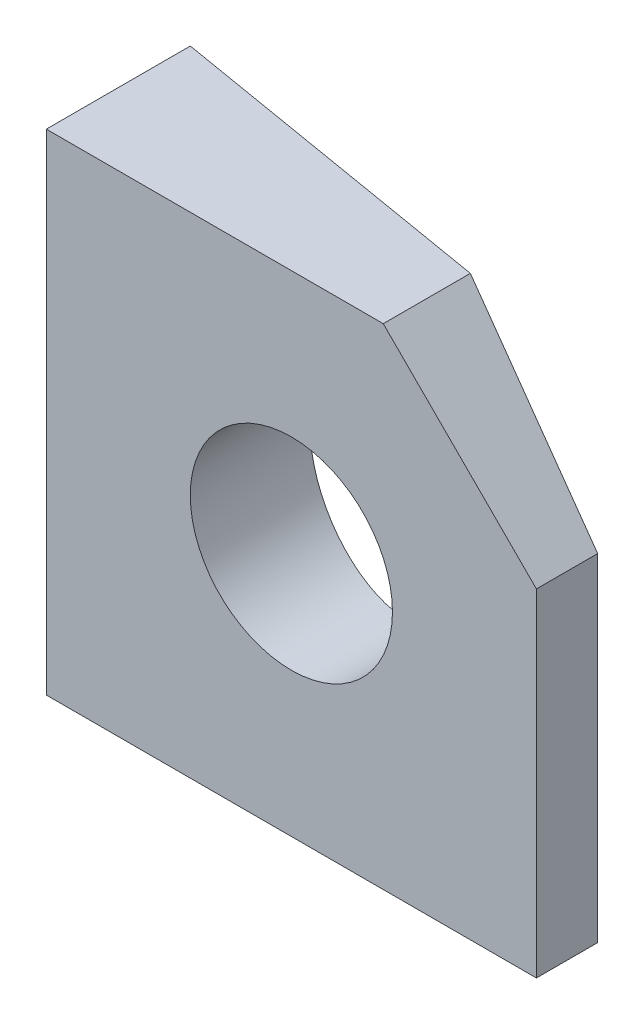
SolidWorks part; units mm, degrees
ref_plane "Front" through (0, 0, 0) normal (0, 0, 1) x (1, 0, 0)
ref_plane "Top" through (0, 0, 0) normal (0, 1, 0) x (1, 0, 0)
ref_plane "Right" through (0, 0, 0) normal (1, 0, 0) x (0, 0, -1)
sketch "Sketch1" plane through (0, 0, 0) normal (0, 0, 1) x (1, 0, 0)
  line L1 (8, 8) -> (-8, 8)
  line L2 (-8, 8) -> (-8, -8)
  line L3 (-8, -8) -> (8, -8)
  line L4 (8, -8) -> (8, 8)
  circle A0 centre (0, 0) radius 8 construction
  circle A1 centre (0, 0) radius 3.3
  dimension "d" = 6.6
  dimension "B" = 16
extrude "Base-Extrude" add sketch "Sketch1" against normal blind 4.7
sketch "Sketch2" plane through (-0.2147, 8, -3.4984) normal (0, 1, 0) x (-1, 0, 0)
  line L0 (-8.2147, -1.2016) -> (7.7853, -1.2016)
  line L1 (7.7853, -1.2016) -> (-8.2147, 1.4984)
  line L3 (-8.2147, 1.4984) -> (-8.2147, -1.2016)
  dimension "H" = 2
extrude "Cut-Extrude1" cut sketch "Sketch2" against normal through all
chamfer "Chamfer1" distance 5 angle 45 1 edges at (8, 8, -1)
